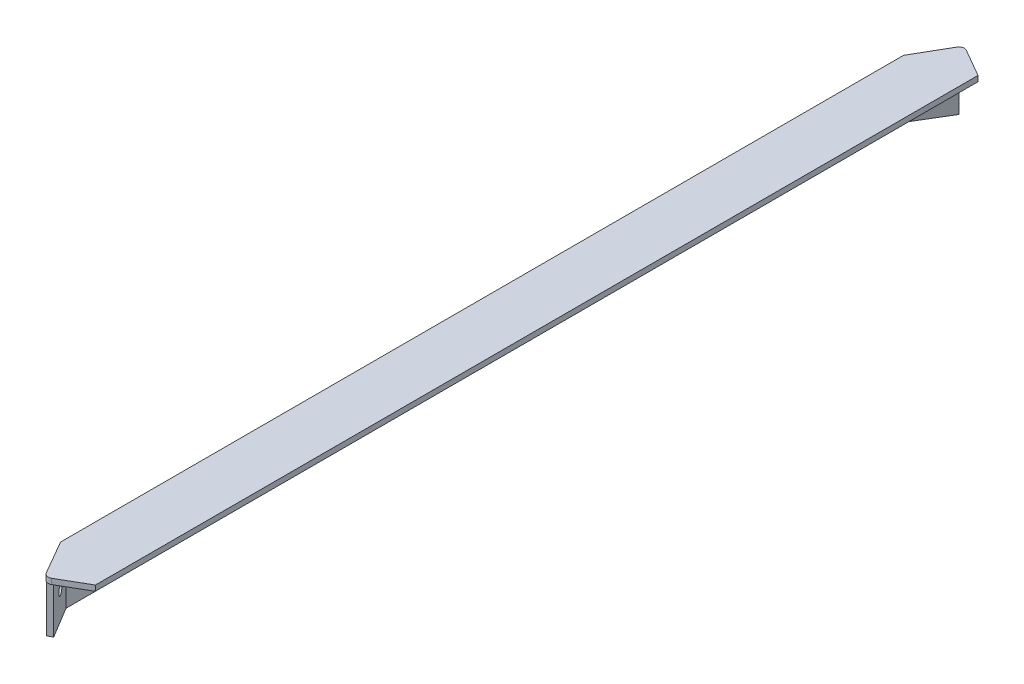
SolidWorks part; units mm, degrees
ref_plane "Front Plane" through (0, 0, 0) normal (0, 0, 1) x (1, 0, 0)
ref_plane "Top Plane" through (0, 0, 0) normal (0, 1, 0) x (1, 0, 0)
ref_plane "Right Plane" through (0, 0, 0) normal (1, 0, 0) x (0, 0, -1)
sketch "Sketch1" plane through (0, 0, 0) normal (0, 0, 1) x (1, 0, 0)
  line L6 (0, 0) -> (0, 70)
  line L7 (0, 70) -> (70, 70)
  line L8 (70, 70) -> (70, 63)
  line L9 (70, 63) -> (7, 63)
  line L10 (7, 63) -> (7, 0)
  line L11 (7, 0) -> (0, 0)
  dimension "D1" = 70
  dimension "D2" = 70
  dimension "D3" = 7
  dimension "D4" = 7
extrude "Boss-Extrude1" add sketch "Sketch1" along normal blind 540
sketch "Sketch2" plane through (0, 0, 0) normal (0, 1, 0) x (1, 0, 0)
  line L0 (0, -540) -> (25, -583.3013)
  line L1 (25, -583.3013) -> (31.0622, -579.8013)
  line L2 (31.0622, -579.8013) -> (7, -540)
  line L3 (0, -540) -> (7, -540) construction
  line L4 (7, -540) -> (0, -540)
  line L5 (0, -540) -> (0, 0) construction
  dimension "D1" = 46.5095
  dimension "D2" = 50
  dimension "D3" = 210
  dimension "D4" = 7
extrude "Boss-Extrude2" add sketch "Sketch2" along normal blind 63
sketch "Sketch9" plane through (0, 63, 0) normal (0, 1, 0) x (1, 0, 0)
  line L0 (0, -540) -> (25, -583.3013)
  line L1 (34.5622, -585.8634) -> (70, -565.4034)
  line L2 (70, -565.4034) -> (70, -540)
  line L3 (70, -540) -> (0, -540)
  arc A0 (25, -583.3013) -> (34.5622, -585.8634) centre (31.0622, -579.8013) ccw
  dimension "D5" = 14
  dimension "D2" = 40.9201
  dimension "D1" = 90
  dimension "D3" = 90
  dimension "D4" = 60
  dimension "D6" = 7
  dimension "D7" = 7
extrude "Boss-Extrude4" add sketch "Sketch9" along normal blind 7
sketch "Sketch10" plane through (-233.9536, 0, 141.4385) normal (0.8558, 0, -0.5174) x (-0.5174, 0, -0.8558)
  line L0 (-512.2453, 63) -> (-512.2453, 0) construction
  line L1 (-512.2453, 0) -> (-465.7359, 0) construction
  circle A0 centre (-487.2453, 35) radius 6
  dimension "D1" = 12
  dimension "D2" = 25
  dimension "D3" = 35
extrude "Cut-Extrude3" cut sketch "Sketch10" against normal blind 7
sketch "Sketch21" plane through (0, 0, 0) normal (0, 0, -1) x (-1, 0, 0)
  line L0 (0, 70) -> (-70, 70) construction
  line L1 (-70, 70) -> (-70, 0) construction
  line L2 (-70, 0) -> (0, 0) construction
  line L3 (0, 0) -> (0, 69.2595) construction
fillet "Fillet5" radius 5 2 edges at (19.0311, 63, 559.9006) (7, 63, 270)
mirror "Mirror6" about plane through (0, 0, 0) normal (0, 0, 1) of bodies 107 108
